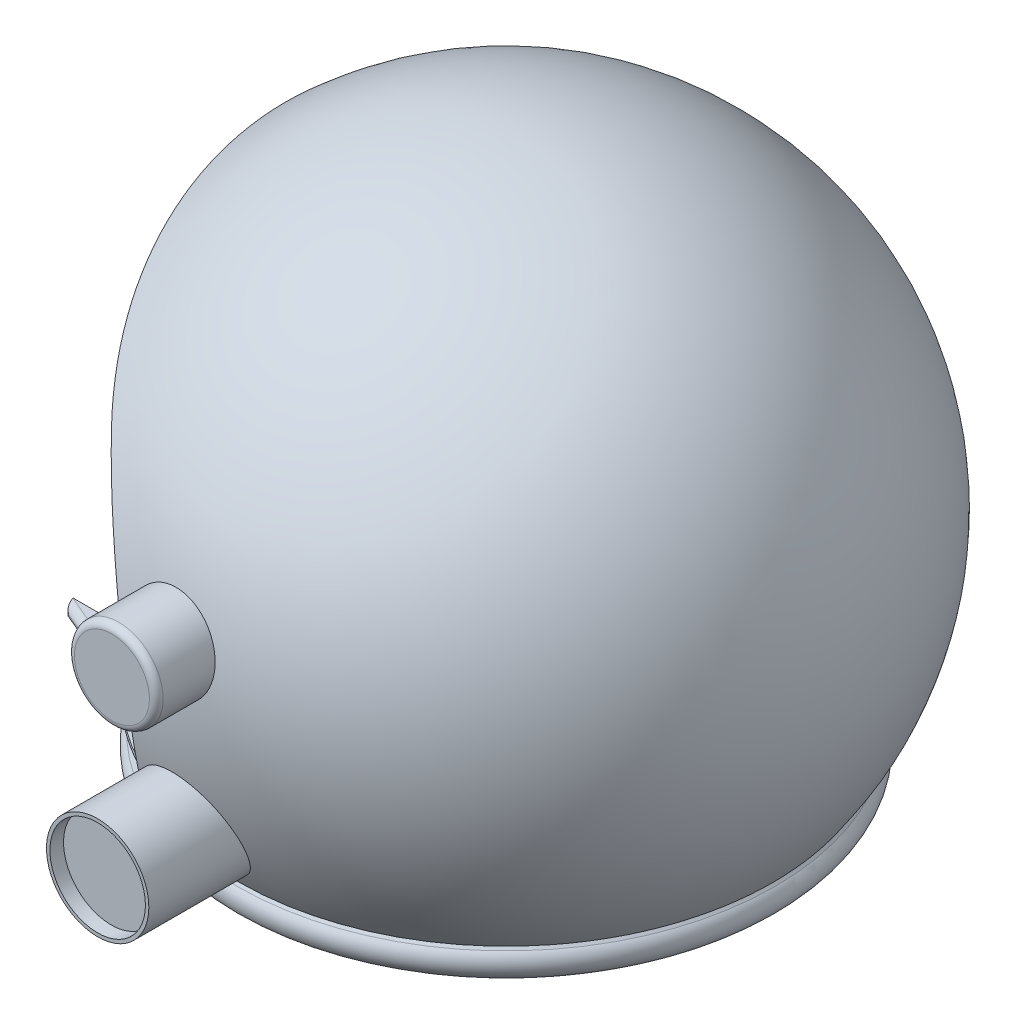
SolidWorks part; units mm, degrees
ref_plane "Front Plane" through (0, 0, 0) normal (0, 0, 1) x (1, 0, 0)
ref_plane "Top Plane" through (0, 0, 0) normal (0, 1, 0) x (1, 0, 0)
ref_plane "Right Plane" through (0, 0, 0) normal (1, 0, 0) x (0, 0, -1)
sketch "Sketch1" plane through (0, 0, 0) normal (0, 0, 1) x (1, 0, 0)
  line L2 (-32.314, 35.4937) -> (-30.2944, 33.2753)
  line L3 (44.6337, 5.7298) -> (47.6093, 6.1118)
  arc A0 (44.6337, 5.7298) -> (-30.2944, 33.2753) centre (0, 0) ccw
  arc A1 (-32.314, 35.4937) -> (47.6093, 6.1118) centre (0, 0) cw
  dimension "D4" = 48
  dimension "D1" = 45
revolve "Revolve2" add sketch "Sketch1" angle 360 about L3
sketch "Sketch2" plane through (0, 0, 0) normal (0, 0, 1) x (1, 0, 0)
  line L0 (-32.314, 35.4937) -> (-18.8554, 20.7108)
  line L1 (-13.0128, -24.8018) -> (-22.3011, -42.5048)
  line L2 (-22.3011, -42.5048) -> (-32.314, 35.4937)
  line L3 (-22.3011, -42.5048) -> (-32.314, 35.4937) construction
  arc A1 (-18.8554, 20.7108) -> (-13.0128, -24.8018) centre (-48.4335, -6.2176) cw
  point P21 (0, 0)
  dimension "D1" = 40
extrude "Cut-Extrude1" cut sketch "Sketch2" against normal through all both and the other way through all
ref_plane "Plane1" through (0, -48, 0) normal (0, 1, 0) x (1, 0, 0)
sketch "Sketch4" plane through (0, -48, 0) normal (0, 1, 0) x (1, 0, 0)
  circle A0 centre (0, 0) radius 37.5
  dimension "D1" = 75
extrude "Cut-Extrude2" cut sketch "Sketch4" along normal blind 30
sketch "Sketch7" plane through (0, 0, 0) normal (1, 0, 0) x (0, 0, -1)
  line L0 (0, 0) -> (0, -29.9625) construction
  line L1 (37.5, -29.9625) -> (-37.5, -29.9625) construction
  line L2 (-39.8784, -23.5877) -> (-35.1452, -23.5877)
  line L5 (-37.5, -29.9625) -> (-37.5, -23.5877) construction
  arc A0 (-39.3472, -28.2778) -> (-35.6528, -28.2778) centre (-37.5, -29.9625) ccw
  spline S0 degree 3 poles (-39.8784, -23.5877) (-40.3013, -25.4313) (-36.6467, -24.6532) (-39.3472, -28.2778) knots 0 0 0 0 1 1 1 1
  spline S1 degree 2 poles (-35.1452, -23.5877) (-37.467, -25.6304) (-35.6528, -28.2778) knots 0 0 0 1 1 1
  dimension "D1" = 5
revolve "Revolve3" add sketch "Sketch7" angle 360 about L0
ref_plane "Plane4" through (0, 0, 48) normal (0, 0, 1) x (1, 0, 0)
sketch "Sketch8" plane through (0, 0, 48) normal (0, 0, 1) x (1, 0, 0)
  circle A0 centre (-1.8748, -18.7517) radius 7.5
  dimension "D1" = 15
extrude "Boss-Extrude1" add sketch "Sketch8" along normal blind 10 and the other way blind 7
sketch "Sketch9" plane through (0, 0, 58) normal (0, 0, 1) x (1, 0, 0)
  circle A0 centre (-1.8748, -18.7517) radius 7
  circle A1 centre (-1.8748, -18.7517) radius 7.5 construction
  dimension "D1" = 14
extrude "Cut-Extrude3" cut sketch "Sketch9" against normal blind 2
sketch "Sketch10" plane through (0, 0, 56) normal (0, 0, 1) x (1, 0, 0)
  circle A0 centre (-1.7851, 5.7337) radius 6.5
  dimension "D1" = 13
extrude "Boss-Extrude2" add sketch "Sketch10" against normal blind 16
ref_plane "Plane5" through (0, 6, 0) normal (0, 1, 0) x (1, 0, 0)
sketch "Sketch13" plane through (0, 6, 0) normal (0, 1, 0) x (1, 0, 0)
  line L0 (-8.2851, -50.0477) -> (-13.4291, -50.0477)
  line L1 (-13.4291, -50.0477) -> (-13.0095, -51.3488)
  line L2 (-13.0095, -51.3488) -> (-8.2851, -53.341)
  line L3 (-8.2851, -50.0477) -> (-8.2851, -53.341)
  line L4 (-8.2851, -46.9306) -> (-8.2851, -56) construction
  line L5 (-8.2851, -56) -> (4.7149, -56) construction
extrude "Boss-Extrude3" add sketch "Sketch13" along normal blind 1 and the other way blind 1 separate body
fillet "Fillet1" radius 1 1 edges at (4.7149, 5.7337, 56)
fillet "Fillet2" radius 1 4 edges at (-10.6473, 5, 52.3449) (-13.0095, 6, 51.3488) (-10.6473, 7, 52.3449) (-8.2851, 6, 53.341)
